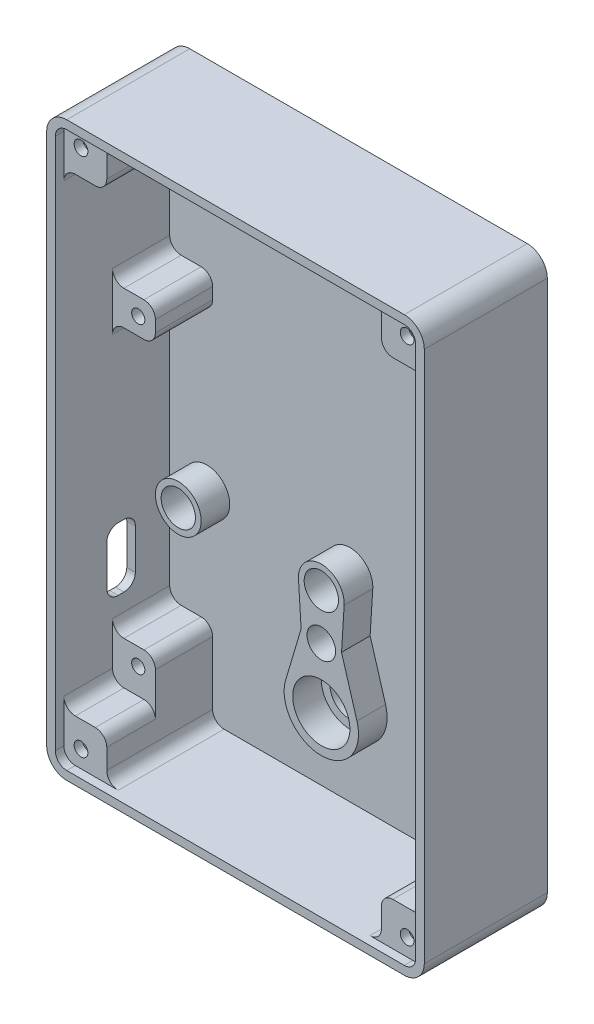
SolidWorks part; units mm, degrees
material "ABS"
ref_plane "Спереди" through (0, 0, 0) normal (0, 0, 1) x (1, 0, 0)
ref_plane "Сверху" through (0, 0, 0) normal (0, 1, 0) x (1, 0, 0)
ref_plane "Справа" through (0, 0, 0) normal (1, 0, 0) x (0, 0, -1)
sketch "Эскиз1" plane through (0, 0, 0) normal (0, 0, 1) x (1, 0, 0)
  line L1 (-33, -50) -> (33, -50)
  line L2 (-33, -50) -> (-33, 50)
  line L3 (-33, 50) -> (33, 50)
  line L4 (33, -50) -> (33, 50)
  line L5 (-33, -50) -> (33, 50) construction
  line L6 (-33, 50) -> (33, -50) construction
  line L7 (-31.5, -48.5) -> (31.5, -48.5)
  line L8 (-31.5, -48.5) -> (-31.5, 48.5)
  line L9 (-31.5, 48.5) -> (31.5, 48.5)
  line L10 (31.5, -48.5) -> (31.5, 48.5)
  line L11 (-31.5, -48.5) -> (31.5, 48.5) construction
  line L12 (-31.5, 48.5) -> (31.5, -48.5) construction
  point P0 (0, 0)
  point P6 (0, 0)
  dimension "D1" = 66
  dimension "D2" = 100
  dimension "D3" = 1.5
  dimension "D4" = 1.5
extrude "Бобышка-Вытянуть1" add sketch "Эскиз1" along normal blind 20
sketch "Эскиз3" plane through (0, 0, 0) normal (0, 0, -1) x (-1, 0, 0)
  line L1 (-33, 50) -> (33, 50)
  line L2 (-33, 50) -> (-33, -50)
  line L3 (-33, -50) -> (33, -50)
  line L4 (33, 50) -> (33, -50)
extrude "Бобышка-Вытянуть2" add sketch "Эскиз3" along normal blind 1.5
sketch "Эскиз4" plane through (0, 0, 0) normal (0, 0, 1) x (1, 0, 0)
  line L0 (-31.5, 48.5) -> (-31.5, -48.5) construction
  line L1 (-31.5, 19.5) -> (-24, 19.5)
  line L2 (-31.5, 19.5) -> (-31.5, 13.5)
  line L3 (-31.5, 13.5) -> (-24, 13.5)
  line L4 (-24, 19.5) -> (-24, 13.5)
  line L5 (31.5, -48.5) -> (31.5, 48.5) construction
  line L6 (31.5, 19.5) -> (24, 19.5)
  line L7 (31.5, 19.5) -> (31.5, 13.5)
  line L8 (31.5, 13.5) -> (24, 13.5)
  line L9 (24, 19.5) -> (24, 13.5)
  line L10 (-31.5, -48.5) -> (31.5, -48.5) construction
  line L11 (-31.5, -41) -> (-24, -41)
  line L12 (-31.5, -41) -> (-31.5, -33.5)
  line L13 (-31.5, -33.5) -> (-24, -33.5)
  line L14 (-24, -41) -> (-24, -33.5)
  line L15 (31.5, -41) -> (24, -41)
  line L16 (31.5, -41) -> (31.5, -33.5)
  line L17 (31.5, -33.5) -> (24, -33.5)
  line L18 (24, -41) -> (24, -33.5)
  line L19 (31.5, -48.5) -> (31.5, 48.5) construction
  dimension "D1" = 7.5
  dimension "D2" = 7.5
  dimension "D3" = 6
  dimension "D4" = 47
  dimension "D5" = 7.5
extrude "Бобышка-Вытянуть3" add sketch "Эскиз4" along normal blind 10
sketch "Эскиз5" plane through (0, 0, 10) normal (0, 0, 1) x (1, 0, 0)
  line L0 (-24, 13.5) -> (-24, 19.5) construction
  line L1 (24, 19.5) -> (24, 13.5) construction
  line L2 (-31.5, 13.5) -> (-24, 13.5) construction
  line L3 (-24, -33.5) -> (-31.5, -33.5) construction
  point P0 (-27, 16.5)
  point P1 (27, 16.5)
  point P2 (27, -36.5)
  point P3 (-27, -36.5)
  dimension "D1" = 3
  dimension "D2" = 3
  dimension "D3" = 3
  dimension "D4" = 3
hole_wizard "Сверло под метчик  спиральное M2.21" positions "Эскиз6" profile "Эскиз7" hole size "M2.2x0.45" standard "DIN"
sketch "Эскиз6" plane through (0, 0, 10) normal (0, 0, 1) x (1, 0, 0)
  point P0 (-27, 16.5)
  point P3 (27, 16.5)
  point P6 (27, -36.5)
  point P9 (-27, -36.5)
sketch "Эскиз7" plane through (-27, 16.5, 10) normal (1, 0, 0) x (0, -1, 0)
  line L0 (0, 0) -> (0, 4.691)
  line L1 (0, 4.691) -> (1.15, 4)
  line L2 (1.15, 4) -> (1.15, 0)
  line L5 (1.15, 0) -> (0, 0)
  line L10 (0, 4.691) -> (-1.15, 4) construction
  line L11 (0, -6.35) -> (0, 107.95) construction
  dimension "Диаметр отверстия" = 2.3
  dimension "Глубина отверстия" = 4
  dimension "Угол заточки сверла" = 118
sketch "Эскиз8" plane through (0, 0, 0) normal (0, 0, 1) x (1, 0, 0)
  line L0 (-24, -41) -> (-24, -33.5) construction
  line L1 (-31.5, 48.5) -> (-24, 48.5)
  line L2 (-31.5, 48.5) -> (-31.5, 41)
  line L3 (-31.5, 41) -> (-24, 41)
  line L4 (-24, 48.5) -> (-24, 41)
  line L5 (31.5, 48.5) -> (24, 48.5)
  line L6 (31.5, 48.5) -> (31.5, 41)
  line L7 (31.5, 41) -> (24, 41)
  line L8 (24, 48.5) -> (24, 41)
  line L9 (31.5, -48.5) -> (24, -48.5)
  line L10 (31.5, -48.5) -> (31.5, -41)
  line L11 (31.5, -41) -> (24, -41)
  line L12 (24, -48.5) -> (24, -41)
  line L13 (-31.5, -48.5) -> (-24, -48.5)
  line L14 (-31.5, -48.5) -> (-31.5, -41)
  line L15 (-31.5, -41) -> (-24, -41)
  line L16 (-24, -48.5) -> (-24, -41)
  line L18 (24, -33.5) -> (24, -41) construction
  line L19 (-24, 19.5) -> (-31.5, 19.5) construction
  line L21 (-31.5, -41) -> (-24, -41) construction
extrude "Бобышка-Вытянуть4" add sketch "Эскиз8" along normal blind 18.5
fillet "Скругление1" radius 2 20 edges at (-31.5, -33.5, 5) (-24, -33.5, 5) (-24, -48.5, 9.25) (24, -48.5, 9.25) (24, -33.5, 5) (31.5, -33.5, 5) (31.5, 13.5, 5) (24, 13.5, 5) (24, 19.5, 5) (31.5, 19.5, 5) (-31.5, 13.5, 5) (-24, 13.5, 5) (-24, 19.5, 5) (-31.5, 19.5, 5) (-31.5, 41, 9.25) (-24, 41, 9.25) (-24, 48.5, 9.25) (31.5, 41, 9.25) (24, 48.5, 9.25) (24, 41, 9.25)
fillet "Скругление3" radius 2 8 edges at (-31.5, -48.5, 19.25) (-31.5, -41, 14.25) (-24, -41, 14.25) (31.5, -48.5, 19.25) (24, -41, 14.25) (31.5, -41, 14.25) (-31.5, 48.5, 19.25) (31.5, 48.5, 19.25)
fillet "Скругление4" radius 3.5 4 edges at (-33, -50, 9.25) (33, -50, 9.25) (33, 50, 9.25) (-33, 50, 9.25)
sketch "Эскиз9" plane through (0, 0, 0) normal (0, 0, 1) x (1, 0, 0)
  line L2 (26, -41) -> (29.5, -41) construction
  circle A0 centre (-25, -14) radius 3
  circle A1 centre (25, -14) radius 3
  circle A2 centre (0, -22) radius 2.5
  circle A3 centre (0, -14) radius 3
  circle A4 centre (0, -32.5) radius 3.5
  dimension "D1" = 6
  dimension "D6" = 7
  dimension "D8" = 5
  dimension "D2" = 8
  dimension "D3" = 10.5
  dimension "D4" = 25
  dimension "D5" = 25
  dimension "D7" = 8.5
extrude "Вырез-Вытянуть1" cut sketch "Эскиз9" against normal through all
sketch "Эскиз10" plane through (0, 0, 0) normal (0, 0, 1) x (1, 0, 0)
  line L0 (3.9922, -14.25) -> (3.4932, -22.2188)
  line L1 (-3.9922, -14.25) -> (-3.4932, -22.2188)
  line L2 (-6.229, -30.6429) -> (-3.3541, -21)
  line L3 (3.3541, -21) -> (6.229, -30.6429)
  circle A0 centre (-25, -14) radius 3
  circle A1 centre (0, -22) radius 2.5 construction
  circle A2 centre (0, -14) radius 3
  circle A3 centre (25, -14) radius 3
  circle A4 centre (0, -22) radius 2.5
  circle A5 centre (-25, -14) radius 3 construction
  circle A6 centre (0, -14) radius 4
  circle A7 centre (25, -14) radius 4
  arc A8 (3.3541, -21) -> (-3.3541, -21) centre (0, -22) ccw
  circle A9 centre (-25, -14) radius 4
  circle A10 centre (0, -32.5) radius 6.5
  circle A11 centre (0, -32.5) radius 5
  arc A12 (-3.4932, -22.2188) -> (3.4932, -22.2188) centre (0, -22) ccw
  circle M1 centre (-25, -14) radius 3
  circle M2 centre (0, -14) radius 3
  circle M3 centre (0, -22) radius 2.5
  circle M4 centre (25, -14) radius 3
  dimension "D1" = 1
  dimension "D2" = 1
  dimension "D3" = 1.5
  dimension "D4" = 10
extrude "Бобышка-Вытянуть5" add sketch "Эскиз10" along normal blind 5 contours A6 M2 | A8 L3 L0 A6 L1 L2 | L1 A12 L0 L3 A8 L2 M3 | A12 L1 L2 A10 L3 L0 | A10 A11 | A9 M1 | A7 M4 region at (0, -18.2536, 0) region at (0, -17.8869, 0) region at (0, -25.6701, 0) region at (3.4134, -21.9017, 0) region at (6.25, -31.5881, 0) region at (21.1131, -14, 0) region at (-28.8869, -14, 0)
sketch "Эскиз11" plane through (0, 0, -1.5) normal (0, 0, -1) x (-1, 0, 0)
  line L0 (29.5, 50) -> (-29.5, 50) construction
  line L1 (33, -46.5) -> (33, 46.5) construction
  line L2 (-29.5, -50) -> (29.5, -50) construction
  line L3 (-33, 46.5) -> (-33, -46.5) construction
  circle A0 centre (-28.5, 45.5) radius 2.5
  circle A1 centre (28.5, 45.5) radius 2.5
  circle A2 centre (28.5, -45.5) radius 2.5
  circle A3 centre (-28.5, -45.5) radius 2.5
  dimension "D2" = 5
  dimension "D1" = 4.5
  dimension "D3" = 4.5
  dimension "D4" = 4.5
  dimension "D5" = 4.5
extrude "Вырез-Вытянуть2" cut sketch "Эскиз11" against normal blind 18.5
sketch "Эскиз12" plane through (0, 0, 17) normal (0, 0, -1) x (-1, 0, 0)
  point P0 (-28.5, 45.5)
  point P1 (28.5, 45.5)
  point P3 (28.5, -45.5)
  point P5 (-28.5, -45.5)
hole_wizard "Отверстие с зазором M21" positions "Эскиз13" profile "Эскиз14" hole size "M2" standard "DIN" end condition through all
sketch "Эскиз13" plane through (0, 0, 17) normal (0, 0, -1) x (-1, 0, 0)
  point P0 (-28.5, 45.5)
  point P3 (28.5, 45.5)
  point P6 (28.5, -45.5)
  point P9 (-28.5, -45.5)
sketch "Эскиз14" plane through (28.5, 45.5, 17) normal (1, 0, 0) x (0, 1, 0)
  line L0 (0, 0) -> (0, 3)
  line L1 (0, 3) -> (1.2, 3)
  line L2 (1.2, 3) -> (1.2, 0)
  line L5 (1.2, 0) -> (0, 0)
  line L11 (0, -6.35) -> (0, 107.95) construction
  dimension "Диаметр сквозного отверстия" = 2.4
  dimension "Глубина сквозного отверстия" = 3
sketch "Эскиз15" plane through (-31.5, 0, 0) normal (-1, 0, 0) x (0, 0, 1)
  line L1 (6, -28.5) -> (11, -28.5)
  line L2 (6, -28.5) -> (6, -17.5)
  line L3 (6, -17.5) -> (11, -17.5)
  line L4 (11, -28.5) -> (11, -17.5)
  line L5 (10, -39) -> (10, -31.5) construction
  dimension "D1" = 5
  dimension "D2" = 11
  dimension "D3" = 8
  dimension "D4" = 1
extrude "Вырез-Вытянуть3" cut sketch "Эскиз15" along normal up to surface (1.5 mm away) up to face at (-33, 0, 9.25)
fillet "Скругление5" radius 2 4 edges at (-32.25, -28.5, 11) (-32.25, -17.5, 11) (-32.25, -17.5, 6) (-32.25, -28.5, 6)
sketch "Эскиз16" plane through (0, 0, 0) normal (0, 0, 1) x (1, 0, 0)
  circle A0 centre (0, -32.5) radius 5
  circle A1 centre (0, -32.5) radius 6.5
  dimension "D1" = 1.5
  dimension "D2" = 10
extrude "Бобышка-Вытянуть6" [suppressed] add sketch "Эскиз16" along normal blind 5
sketch "Эскиз20" plane through (-33, 0, 0) normal (1, 0, 0) x (0, 0, -1)
  line L0 (-16, -9.5) -> (-16, -8)
  line L1 (-16, -8) -> (-1.5, -15)
  line L2 (-1.5, -15) -> (-1.5, -16.5)
  line L3 (-1.5, -16.5) -> (-16, -9.5)
  line L4 (-20, -46.5) -> (-20, 46.5) construction
  line L5 (1.5, 46.5) -> (1.5, -46.5) construction
  line L7 (-9, -17.5) -> (-8, -17.5) construction
  dimension "D1" = 1.5
  dimension "D2" = 4
  dimension "D3" = 3
  dimension "D4" = 7
  dimension "D5" = 1
extrude "Бобышка-Вытянуть8" add sketch "Эскиз20" against normal blind 2
